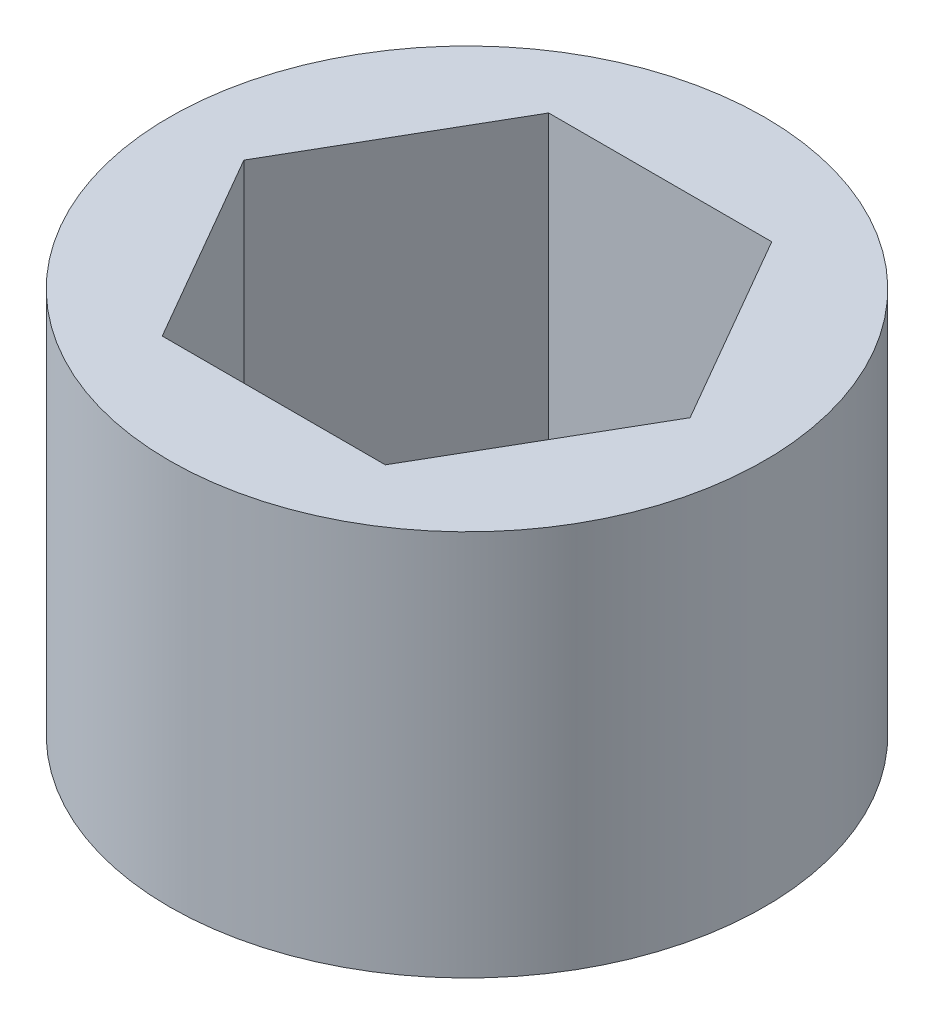
SolidWorks part; units mm, degrees
material "Nylon 101"
ref_plane "Front Plane" through (0, 0, 0) normal (0, 0, 1) x (1, 0, 0)
ref_plane "Top Plane" through (0, 0, 0) normal (0, 1, 0) x (1, 0, 0)
ref_plane "Right Plane" through (0, 0, 0) normal (1, 0, 0) x (0, 0, -1)
sketch "Sketch1" plane through (0, 0, 0) normal (0, 1, 0) x (1, 0, 0)
  line L1 (-3.6662, 6.35) -> (-7.3323, 0)
  line L2 (-7.3323, 0) -> (-3.6662, -6.35)
  line L3 (-3.6662, -6.35) -> (3.6662, -6.35)
  line L4 (3.6662, -6.35) -> (7.3323, 0)
  line L5 (7.3323, 0) -> (3.6662, 6.35)
  line L6 (3.6662, 6.35) -> (-3.6662, 6.35)
  circle A0 centre (0, 0) radius 9.779
  circle A1 centre (0, 0) radius 6.35 construction
  dimension "D1" = 12.7
  dimension "D2" = 19.558
extrude "Boss-Extrude1" add sketch "Sketch1" against normal mid plane 12.7
equation "\"Length\"= 0.5"
equation "\"D1@Boss-Extrude1\"=\"Length\""
